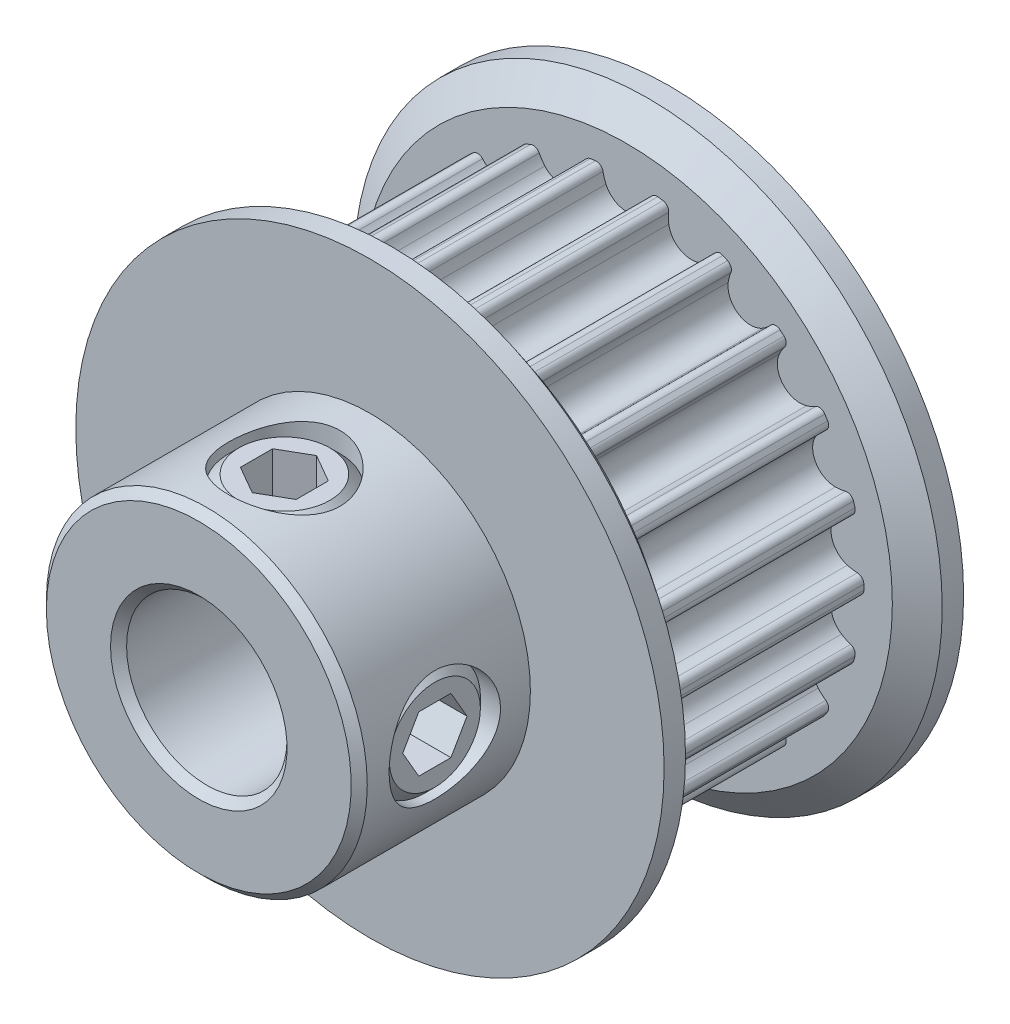
SolidWorks part; units mm, degrees
ref_plane "Front Plane" through (0, 0, 0) normal (0, 0, 1) x (1, 0, 0)
ref_plane "Top Plane" through (0, 0, 0) normal (0, 1, 0) x (1, 0, 0)
ref_plane "Right Plane" through (0, 0, 0) normal (1, 0, 0) x (0, 0, -1)
sketch "Sketch1" plane through (0, 0, 0) normal (0, 0, 1) x (1, 0, 0)
  line L1 (-2.6108, 7.729) -> (2.6108, 7.729) construction
  line L4 (0, 0) -> (0, 7.729) construction
  line L5 (0, 7.729) -> (0, 13.1361) construction
  line L6 (0, 9.25) -> (2.9603, 8.7635) construction
  line L7 (2.9603, 8.7635) -> (3.9948, 8.4141) construction
  line L8 (2.9603, 8.7635) -> (2.6108, 7.729) construction
  line L9 (-2.9603, 8.7635) -> (-2.6108, 7.729) construction
  line L10 (-2.8384, 8.4026) -> (-3.7158, 11)
  line L11 (-3.7158, 11) -> (3.7158, 11)
  line L12 (3.7158, 11) -> (2.8384, 8.4026)
  circle A0 centre (0, 0) radius 9.25 construction
  circle A1 centre (0, 0) radius 11 construction
  circle A2 centre (0, 0) radius 8.869 construction
  arc A3 (-0.7739, 8.2274) -> (0.7739, 8.2274) centre (0, 8.579) ccw
  arc A4 (-0.7739, 8.2274) -> (-0.8862, 8.5883) centre (0.61, 8.8561) cw
  arc A5 (-2.8384, 8.4026) -> (-1.1652, 8.7921) centre (0, 0) cw
  arc A6 (-0.8862, 8.5883) -> (-1.1652, 8.7921) centre (-1.1323, 8.5443) ccw
  arc A7 (2.8384, 8.4026) -> (1.1652, 8.7921) centre (0, 0) ccw
  arc A8 (0.8862, 8.5883) -> (1.1652, 8.7921) centre (1.1323, 8.5443) cw
  arc A9 (0.7739, 8.2274) -> (0.8862, 8.5883) centre (-0.61, 8.8561) ccw
  point P6 (0, 20.9083)
  point P11 (0, 9.25)
  point P13 (0, 11)
  point P14 (0, 8.869)
  dimension "D1" = 7.7722
  dimension "D2" = 3.8861
sketch "Sketch2" plane through (0, 0, 0) normal (1, 0, 0) x (0, 0, -1)
  line L0 (-8.8, 3) -> (8.8, 3)
  line L1 (-8.8, 3) -> (-8.8, 6)
  line L2 (-8.8, 6) -> (-2.4, 6)
  line L3 (-2.4, 6) -> (-2.4, 11)
  line L4 (-2.4, 11) -> (-0.8, 11) construction
  line L5 (-0.8, 11) -> (-0.8, 8.869) construction
  line L6 (-0.8, 8.869) -> (7.2, 8.869)
  line L7 (7.2, 8.869) -> (7.2, 11) construction
  line L8 (7.2, 11) -> (8.8, 11) construction
  line L9 (8.8, 11) -> (8.8, 3)
  line L10 (-8.8, 0) -> (8.8, 0) construction
  line L11 (8, 11) -> (7.2, 9.9345)
  line L12 (-0.8, 9.9345) -> (-1.6, 11)
  line L13 (-2.4, 11) -> (-1.6, 11)
  line L14 (-0.8, 9.9345) -> (-0.8, 8.869)
  line L15 (7.2, 8.869) -> (7.2, 9.9345)
  line L16 (8, 11) -> (8.8, 11)
  arc A0 (-0.8, 9.9345) -> (-1.6, 11) centre (-1.9096, 9.9345) ccw construction
  arc A1 (7.2, 9.9345) -> (8, 11) centre (8.3096, 9.9345) cw construction
  point P12 (-0.8, 9.9345)
  point P14 (-1.6, 11)
  point P20 (7.2, 9.9345)
  point P21 (8, 11)
  point P25 (7.2, 0)
  point P26 (-0.8, 0)
  dimension "D1" = 6.4
  dimension "D2" = 11
revolve "Revolve1" add sketch "Sketch2" angle 360 mid plane about L10
sketch "Sketch3" plane through (0, 0, 0) normal (0, 0, 1) x (1, 0, 0)
  line L6 (3.7158, 11) -> (-3.7158, 11)
  line L7 (2.8384, 8.4026) -> (3.7158, 11)
  line L8 (-3.7158, 11) -> (-2.8384, 8.4026)
  line L9 (3.7158, 11) -> (-3.7158, 11)
  line L10 (2.8384, 8.4026) -> (3.7158, 11)
  line L11 (-3.7158, 11) -> (-2.8384, 8.4026)
  arc A8 (2.8384, 8.4026) -> (1.1652, 8.7921) centre (0, 0) ccw
  arc A9 (1.1652, 8.7921) -> (0.8862, 8.5883) centre (1.1323, 8.5443) ccw
  arc A10 (0.7739, 8.2274) -> (0.8862, 8.5883) centre (-0.61, 8.8561) ccw
  arc A11 (-0.7739, 8.2274) -> (0.7739, 8.2274) centre (0, 8.579) ccw
  arc A12 (-0.8862, 8.5883) -> (-0.7739, 8.2274) centre (0.61, 8.8561) ccw
  arc A13 (-0.8862, 8.5883) -> (-1.1652, 8.7921) centre (-1.1323, 8.5443) ccw
  arc A14 (-1.1652, 8.7921) -> (-2.8384, 8.4026) centre (0, 0) ccw
  arc A15 (2.8384, 8.4026) -> (1.1652, 8.7921) centre (0, 0) ccw
  arc A16 (1.1652, 8.7921) -> (0.8862, 8.5883) centre (1.1323, 8.5443) ccw
  arc A17 (0.7739, 8.2274) -> (0.8862, 8.5883) centre (-0.61, 8.8561) ccw
  arc A18 (-0.7739, 8.2274) -> (0.7739, 8.2274) centre (0, 8.579) ccw
  arc A19 (-0.8862, 8.5883) -> (-0.7739, 8.2274) centre (0.61, 8.8561) ccw
  arc A20 (-0.8862, 8.5883) -> (-1.1652, 8.7921) centre (-1.1323, 8.5443) ccw
  arc A21 (-1.1652, 8.7921) -> (-2.8384, 8.4026) centre (0, 0) ccw
  dimension "D1" = 0
extrude "Cut-Extrude1" cut sketch "Sketch3" against normal up to vertex (7.2 mm away) from vertex up to point (0, 8.869, -7.2) starting at point (0, 8.869, 0.8)
pattern_circular "CirPattern1" count 22 over 360 about axis through (0, 0, 8.8) along (0, 0, 1) of "Cut-Extrude1"
sketch "Sketch4" plane through (0, 0, 0) normal (1, 0, 0) x (0, -1, 0)
  line L0 (0, -2.4) -> (0, -8.8) construction
  line L1 (-6, -2.4) -> (6, -2.4) construction
  line L2 (-6, -8.8) -> (6, -8.8) construction
  circle A0 centre (0, -5.6) radius 2.0828
extrude "Cut-Extrude2" cut sketch "Sketch4" along normal through all
ref_plane "Plane1" through (0, 0, 5.6) normal (0, 0, 1) x (1, 0, 0)
sketch "Sketch5" plane through (0, 0, 5.6) normal (0, 0, 1) x (1, 0, 0)
  line L0 (0, 0.1664) -> (0, 6) construction
  line L1 (3, -1.7018) -> (3, 0)
  line L2 (3.381, -2.0828) -> (5.2459, -2.0828)
  line L3 (3, 0) -> (6, 0) construction
  line L4 (3, 0) -> (5.6269, 0)
  line L5 (5.6269, 0) -> (5.6269, -1.7018)
  line L6 (3.381, -2.0828) -> (3, -1.7018)
  line L7 (5.6269, -1.7018) -> (5.2459, -2.0828)
  circle A0 centre (0, 0) radius 6 construction
  circle A1 centre (0, 0) radius 3 construction
  point P2 (3, -2.0828)
  point P11 (5.6269, -2.0828)
revolve "Revolve2" add sketch "Sketch5" angle 360 mid plane about L4
sketch "Sketch6" plane through (5.6269, 5.3841, 0) normal (-1, 0, 0) x (0, -1, 0)
  line L1 (5.3841, 6.8025) -> (4.3427, 6.2013)
  line L2 (4.3427, 6.2013) -> (4.3427, 4.9987)
  line L3 (4.3427, 4.9987) -> (5.3841, 4.3975)
  line L4 (5.3841, 4.3975) -> (6.4255, 4.9987)
  line L5 (6.4255, 4.9987) -> (6.4255, 6.2013)
  line L6 (6.4255, 6.2013) -> (5.3841, 6.8025)
  circle A0 centre (5.3841, 5.6) radius 1.0414 construction
  dimension "D1" = 2.0828
extrude "Cut-Extrude3" cut sketch "Sketch6" along normal blind 1.5621
pattern_circular "CirPattern2" count 2 over 90 about axis through (0, 0, 8.8) along (0, 0, 1) of "Cut-Extrude2", "Revolve2", "Cut-Extrude3"
chamfer "Chamfer1" distance 0.3 angle 45 2 edges at (3, 0, 8.8) (6, 0, 8.8)
ref_axis "Center Axis 1" through (0, 0, -8.8) along (0, 0, 1)
ref_plane "Contact Plane 1" through (0, 0, 8.8) normal (0, 0, 1) x (1, 0, 0)
ref_plane "Contact Plane 2" through (0, 0, -8.8) normal (0, 0, -1) x (-1, 0, 0)
equation "\"D2@Sketch1\" = \"D1@Sketch1\"/2"
equation "\"D1@Sketch6\" = \"Set Screw@Sketch4\" / 2"
equation "\"D1@Cut-Extrude3\" = \"D1@Sketch6\"*.75"
equation "\"D1@Chamfer1\"=\"Hub Dia@Sketch2\"*.025"
